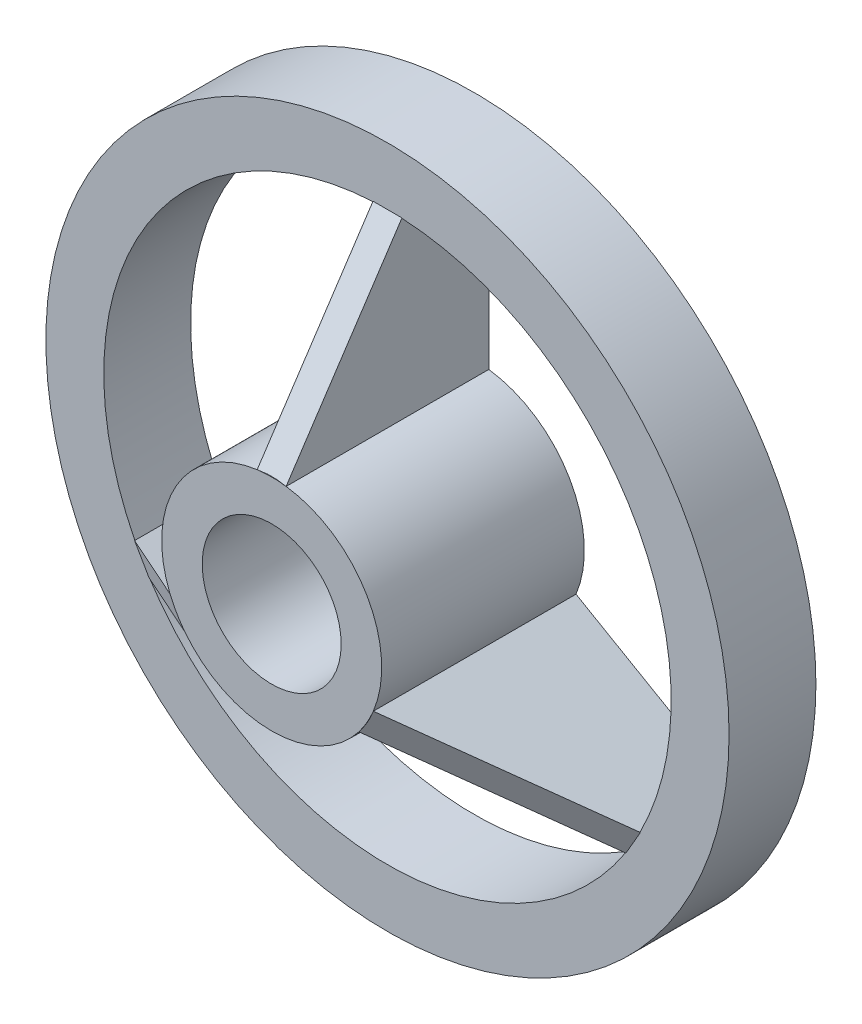
SolidWorks part; units mm, degrees
ref_plane "Front Plane" through (0, 0, 0) normal (0, 0, 1) x (1, 0, 0)
ref_plane "Top Plane" through (0, 0, 0) normal (0, 1, 0) x (1, 0, 0)
ref_plane "Right Plane" through (0, 0, 0) normal (1, 0, 0) x (0, 0, -1)
sketch "Sketch1" plane through (0, 0, 0) normal (0, 0, 1) x (1, 0, 0)
  circle A0 centre (0, 0) radius 1.2
  circle A1 centre (0, 0) radius 1.9
  dimension "D1" = 2.4
  dimension "D2" = 3.8
extrude "Boss-Extrude1" add sketch "Sketch1" along normal blind 3.5
sketch "Sketch2" plane through (0, 0, 0) normal (0, 0, 1) x (1, 0, 0)
  circle A0 centre (0, 0) radius 4.9
  circle A1 centre (0, 0) radius 5.9
  dimension "D1" = 9.8
  dimension "D2" = 11.8
extrude "Boss-Extrude2" add sketch "Sketch2" along normal blind 1.5 separate body contours A0 | A1
sketch "Sketch3" plane through (0, 0, 0) normal (1, 0, 0) x (0, 0, -1)
  line L0 (0, 4.9) -> (-1.5, 4.9)
  line L2 (-1.5, 4.9) -> (-3.5, 1.8852)
  line L3 (-3.5, 1.9) -> (-3.5, -1.9) construction
  line L4 (-3.5, 1.8852) -> (-3.5, 1.6432)
  line L5 (-3.5, 1.6432) -> (0, 1.6432)
  line L6 (0, -5.9) -> (0, 5.9) construction
  line L7 (0, 4.9) -> (0, 1.6432)
  dimension "D1" = 0.242
extrude "Boss-Extrude3" add sketch "Sketch3" along normal mid plane 0.5
ref_axis "Axis1" through (0, 0, 3.5) along (0, 0, -1)
pattern_circular "CirPattern1" count 3 over 360 about axis through (0, 0, 3.5) along (0, 0, -1) of "Boss-Extrude3"
